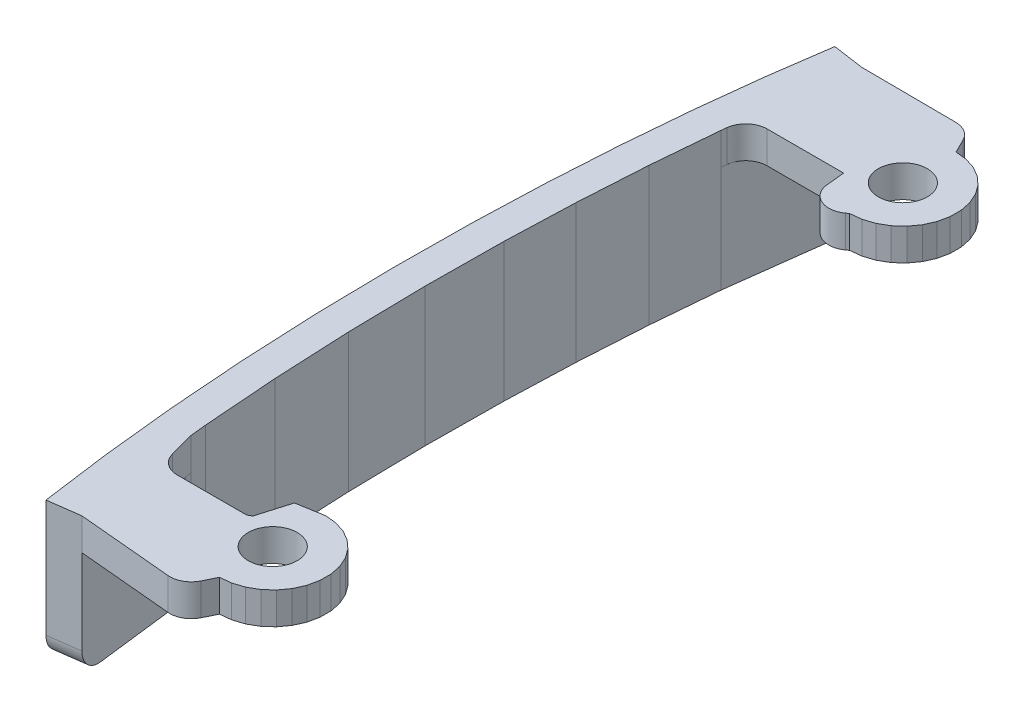
SolidWorks part; units mm, degrees
ref_plane "Płaszczyzna przednia" through (0, 0, 0) normal (0, 0, 1) x (1, 0, 0)
ref_plane "Płaszczyzna górna" through (0, 0, 0) normal (0, 1, 0) x (1, 0, 0)
ref_plane "Płaszczyzna prawa" through (0, 0, 0) normal (1, 0, 0) x (0, 0, -1)
sketch "Szkic2" plane through (0, 0.9904, 0) normal (0, 1, 0) x (1, 0, 0)
  line L0 (-173.5371, -25.6295) -> (-177.9802, -25.6005)
  line L3 (-173.6037, -62.5712) -> (-178.0582, -62.1645)
  line L4 (-179.4653, -25.3891) -> (-179.8753, -28.2702)
  line L5 (-179.8753, -28.2702) -> (-180.2209, -31.3158)
  line L6 (-180.2209, -31.3158) -> (-180.4963, -34.48)
  line L7 (-180.4963, -34.48) -> (-180.6936, -37.7356)
  line L8 (-180.6936, -37.7356) -> (-180.811, -41.0532)
  line L9 (-180.811, -41.0532) -> (-180.8444, -44.7704)
  line L10 (-180.8444, -44.7704) -> (-180.7766, -48.48)
  line L11 (-180.7766, -48.48) -> (-180.6066, -52.1372)
  line L12 (-180.6066, -52.1372) -> (-180.3404, -55.6994)
  line L13 (-180.3404, -55.6994) -> (-179.9818, -59.1279)
  line L14 (-179.9818, -59.1279) -> (-179.5448, -62.3651)
  line L15 (-177.9802, -25.6005) -> (-179.4653, -25.3891)
  line L16 (-178.0582, -62.1645) -> (-179.5448, -62.3651)
  line L17 (-178.8462, -55.5655) -> (-178.4922, -58.9495) construction
  line L18 (-178.7282, -31.4655) -> (-178.7001, -31.2172)
  line L19 (-178.3872, -28.4605) -> (-178.7282, -31.4655) construction
  line L20 (-177.7064, -30.33) -> (-174.1125, -30.33)
  line L22 (-172.3262, -56.4335) -> (-173.5902, -56.6495)
  line L23 (-173.5902, -56.6495) -> (-174.0356, -58.1605)
  line L24 (-174.0356, -58.1605) -> (-174.224, -58.263)
  line L25 (-174.224, -58.263) -> (-177.4828, -58.263)
  line L26 (-178.4487, -57.5219) -> (-178.7651, -56.3415)
  line L27 (-173.8462, -32.9335) -> (-172.3262, -31.8335) construction
  line L28 (-172.4416, -31.9169) -> (-172.3262, -31.8335)
  line L29 (-174.0227, -31.2086) -> (-174.1125, -30.33)
  line L155 (-167.3462, -84.1335) -> (-165.3462, -84.1335)
  line L156 (-165.3462, -84.1335) -> (-164.9012, -84.0835)
  line L157 (-164.9012, -84.0835) -> (-164.4782, -83.9355)
  line L158 (-164.4782, -83.9355) -> (-164.0992, -83.6975)
  line L159 (-164.0992, -83.6975) -> (-163.7822, -83.3805)
  line L160 (-163.7822, -83.3805) -> (-163.5442, -83.0015)
  line L161 (-163.5442, -83.0015) -> (-163.3962, -82.5785)
  line L162 (-163.3962, -82.5785) -> (-163.3462, -82.1335)
  line L163 (-163.3462, -82.1335) -> (-163.3462, -79.1335)
  line L164 (-163.3462, -79.1335) -> (-163.3962, -78.6885)
  line L165 (-163.3962, -78.6885) -> (-163.5442, -78.2655)
  line L166 (-163.5442, -78.2655) -> (-163.7822, -77.8865)
  line L167 (-163.7822, -77.8865) -> (-164.0992, -77.5695)
  line L168 (-164.0992, -77.5695) -> (-164.4782, -77.3315)
  line L169 (-164.4782, -77.3315) -> (-164.9012, -77.1835)
  line L170 (-164.9012, -77.1835) -> (-165.3462, -77.1335)
  line L171 (-165.3462, -77.1335) -> (-167.3462, -77.1335)
  line L172 (-167.3462, -77.1335) -> (-168.1752, -76.2025)
  line L173 (-168.1752, -76.2025) -> (-168.9292, -75.2375)
  line L174 (-168.9292, -75.2375) -> (-169.6902, -74.1145)
  line L175 (-169.6902, -74.1145) -> (-170.3542, -72.9535)
  line L176 (-170.3542, -72.9535) -> (-170.9242, -71.7535)
  line L177 (-170.9242, -71.7535) -> (-171.3582, -70.6365)
  line L178 (-171.3582, -70.6365) -> (-171.7182, -69.4815)
  line L179 (-171.7182, -69.4815) -> (-172.0032, -68.2855)
  line L180 (-172.0032, -68.2855) -> (-172.2152, -67.0325)
  line L181 (-172.2152, -67.0325) -> (-172.3462, -65.7435)
  line L182 (-172.3462, -65.7435) -> (-172.9212, -62.6335)
  line L183 (-172.9212, -62.6335) -> (-172.3262, -61.4335)
  line L184 (-172.3262, -61.4335) -> (-171.8062, -61.3785)
  line L185 (-171.8062, -61.3785) -> (-171.3092, -61.2175)
  line L186 (-171.3092, -61.2175) -> (-170.8562, -60.9565)
  line L187 (-170.8562, -60.9565) -> (-170.4682, -60.6065)
  line L188 (-170.4682, -60.6065) -> (-170.1612, -60.1835)
  line L189 (-170.1612, -60.1835) -> (-169.9482, -59.7065)
  line L190 (-169.9482, -59.7065) -> (-169.8402, -59.1945)
  line L191 (-169.8402, -59.1945) -> (-169.8402, -58.6725)
  line L192 (-169.8402, -58.6725) -> (-169.9482, -58.1605)
  line L193 (-169.9482, -58.1605) -> (-170.1612, -57.6835)
  line L194 (-170.1612, -57.6835) -> (-170.4682, -57.2605)
  line L195 (-170.4682, -57.2605) -> (-170.8562, -56.9105)
  line L196 (-170.8562, -56.9105) -> (-171.3092, -56.6495)
  line L197 (-171.3092, -56.6495) -> (-171.8062, -56.4885)
  line L198 (-171.8062, -56.4885) -> (-172.3262, -56.4335)
  line L199 (-172.3262, -56.4335) -> (-173.8462, -55.3335)
  line L200 (-173.8462, -55.3335) -> (-174.0262, -53.1335)
  line L201 (-174.0262, -53.1335) -> (-171.3462, -53.1335)
  line L202 (-171.3462, -53.1335) -> (-170.9012, -53.0835)
  line L203 (-170.9012, -53.0835) -> (-170.4782, -52.9355)
  line L204 (-170.4782, -52.9355) -> (-170.0992, -52.6975)
  line L205 (-170.0992, -52.6975) -> (-169.7822, -52.3805)
  line L206 (-169.7822, -52.3805) -> (-169.5442, -52.0015)
  line L207 (-169.5442, -52.0015) -> (-169.3962, -51.5785)
  line L208 (-169.3962, -51.5785) -> (-169.3462, -51.1335)
  line L209 (-169.3462, -51.1335) -> (-169.3462, -37.1335)
  line L210 (-169.3462, -37.1335) -> (-169.3962, -36.6885)
  line L211 (-169.3962, -36.6885) -> (-169.5442, -36.2655)
  line L212 (-169.5442, -36.2655) -> (-169.7822, -35.8865)
  line L213 (-169.7822, -35.8865) -> (-170.0992, -35.5695)
  line L214 (-170.0992, -35.5695) -> (-170.4782, -35.3315)
  line L215 (-170.4782, -35.3315) -> (-170.9012, -35.1835)
  line L216 (-170.9012, -35.1835) -> (-171.3462, -35.1335)
  line L217 (-171.3462, -35.1335) -> (-174.0262, -35.1335)
  line L218 (-174.0262, -35.1335) -> (-173.8462, -32.9335)
  line L219 (-173.8462, -32.9335) -> (-172.3262, -31.8335)
  line L220 (-172.3262, -31.8335) -> (-171.8062, -31.7785)
  line L221 (-171.8062, -31.7785) -> (-171.3092, -31.6175)
  line L222 (-171.3092, -31.6175) -> (-170.8562, -31.3565)
  line L223 (-170.8562, -31.3565) -> (-170.4682, -31.0065)
  line L224 (-170.4682, -31.0065) -> (-170.1612, -30.5835)
  line L225 (-170.1612, -30.5835) -> (-169.9482, -30.1065)
  line L226 (-169.9482, -30.1065) -> (-169.8402, -29.5945)
  line L227 (-169.8402, -29.5945) -> (-169.8402, -29.0725)
  line L228 (-169.8402, -29.0725) -> (-169.9482, -28.5605)
  line L229 (-169.9482, -28.5605) -> (-170.1612, -28.0835)
  line L230 (-170.1612, -28.0835) -> (-170.4682, -27.6605)
  line L231 (-170.4682, -27.6605) -> (-170.8562, -27.3105)
  line L232 (-170.8562, -27.3105) -> (-171.3092, -27.0495)
  line L233 (-171.3092, -27.0495) -> (-171.8062, -26.8885)
  line L234 (-171.8062, -26.8885) -> (-172.3262, -26.8335)
  line L235 (-172.3262, -26.8335) -> (-172.9212, -25.6335)
  line L236 (-172.9212, -25.6335) -> (-172.3462, -22.5235)
  line L237 (-172.3462, -22.5235) -> (-172.2152, -21.2345)
  line L238 (-172.2152, -21.2345) -> (-172.0032, -19.9815)
  line L239 (-172.0032, -19.9815) -> (-171.7182, -18.7855)
  line L240 (-171.7182, -18.7855) -> (-171.3582, -17.6305)
  line L241 (-171.3582, -17.6305) -> (-170.9242, -16.5135)
  line L242 (-170.9242, -16.5135) -> (-170.3542, -15.3135)
  line L243 (-170.3542, -15.3135) -> (-169.6902, -14.1525)
  line L244 (-169.6902, -14.1525) -> (-168.9292, -13.0295)
  line L245 (-168.9292, -13.0295) -> (-168.1752, -12.0645)
  line L246 (-168.1752, -12.0645) -> (-167.3462, -11.1335)
  line L247 (-167.3462, -11.1335) -> (-165.3462, -11.1335)
  line L248 (-165.3462, -11.1335) -> (-164.9012, -11.0835)
  line L249 (-164.9012, -11.0835) -> (-164.4782, -10.9355)
  line L250 (-164.4782, -10.9355) -> (-164.0992, -10.6975)
  line L251 (-164.0992, -10.6975) -> (-163.7822, -10.3805)
  line L252 (-163.7822, -10.3805) -> (-163.5442, -10.0015)
  line L253 (-163.5442, -10.0015) -> (-163.3962, -9.5785)
  line L254 (-163.3962, -9.5785) -> (-163.3462, -9.1335)
  line L255 (-163.3462, -9.1335) -> (-163.3462, -6.1335)
  line L256 (-163.3462, -6.1335) -> (-163.3962, -5.6885)
  line L257 (-163.3962, -5.6885) -> (-163.5442, -5.2655)
  line L258 (-163.5442, -5.2655) -> (-163.7822, -4.8865)
  line L259 (-163.7822, -4.8865) -> (-164.0992, -4.5695)
  line L260 (-164.0992, -4.5695) -> (-164.4782, -4.3315)
  line L261 (-164.4782, -4.3315) -> (-164.9012, -4.1835)
  line L262 (-164.9012, -4.1835) -> (-165.3462, -4.1335)
  line L263 (-165.3462, -4.1335) -> (-167.3462, -4.1335)
  line L264 (-167.3462, -4.1335) -> (-167.9032, -4.1765)
  line L265 (-167.9032, -4.1765) -> (-168.4842, -4.3135)
  line L266 (-168.4842, -4.3135) -> (-169.0482, -4.5375)
  line L267 (-169.0482, -4.5375) -> (-169.6222, -4.8595)
  line L268 (-169.6222, -4.8595) -> (-170.2082, -5.2875)
  line L269 (-170.2082, -5.2875) -> (-170.8082, -5.8345)
  line L270 (-170.8082, -5.8345) -> (-171.4912, -6.5955)
  line L271 (-171.4912, -6.5955) -> (-172.1892, -7.5355)
  line L272 (-172.1892, -7.5355) -> (-172.8982, -8.6725)
  line L273 (-172.8982, -8.6725) -> (-173.6142, -10.0245)
  line L274 (-173.6142, -10.0245) -> (-174.3302, -11.6055)
  line L275 (-174.3302, -11.6055) -> (-175.0362, -13.4275)
  line L276 (-175.0362, -13.4275) -> (-175.7252, -15.4985)
  line L277 (-175.7252, -15.4985) -> (-176.3842, -17.8195)
  line L278 (-176.3842, -17.8195) -> (-177.0032, -20.3885)
  line L279 (-177.0032, -20.3885) -> (-177.5162, -22.9035)
  line L280 (-177.5162, -22.9035) -> (-177.9802, -25.6005)
  line L281 (-177.9802, -25.6005) -> (-178.3872, -28.4605)
  line L282 (-178.3872, -28.4605) -> (-178.7282, -31.4655)
  line L283 (-178.7282, -31.4655) -> (-179.0002, -34.5905)
  line L284 (-179.0002, -34.5905) -> (-179.1952, -37.8075)
  line L285 (-179.1952, -37.8075) -> (-179.3112, -41.0865)
  line L286 (-179.3112, -41.0865) -> (-179.3442, -44.7635)
  line L287 (-179.3442, -44.7635) -> (-179.2772, -48.4315)
  line L288 (-179.2772, -48.4315) -> (-179.1092, -52.0465)
  line L289 (-179.1092, -52.0465) -> (-178.8462, -55.5655)
  line L290 (-178.8462, -55.5655) -> (-178.4922, -58.9495)
  line L291 (-178.4922, -58.9495) -> (-178.0582, -62.1645)
  line L292 (-178.0582, -62.1645) -> (-177.5502, -65.1805)
  line L293 (-177.5502, -65.1805) -> (-176.9812, -67.9765)
  line L294 (-176.9812, -67.9765) -> (-176.3612, -70.5355)
  line L295 (-176.3612, -70.5355) -> (-175.7002, -72.8475)
  line L296 (-175.7002, -72.8475) -> (-175.0112, -74.9105)
  line L297 (-175.0112, -74.9105) -> (-174.3742, -76.5555)
  line L298 (-174.3742, -76.5555) -> (-173.7292, -78.0045)
  line L299 (-173.7292, -78.0045) -> (-173.0822, -79.2675)
  line L300 (-173.0822, -79.2675) -> (-172.4392, -80.3515)
  line L301 (-172.4392, -80.3515) -> (-171.8042, -81.2705)
  line L302 (-171.8042, -81.2705) -> (-171.1812, -82.0355)
  line L303 (-171.1812, -82.0355) -> (-170.5722, -82.6605)
  line L304 (-170.5722, -82.6605) -> (-169.9142, -83.2075)
  line L305 (-169.9142, -83.2075) -> (-169.2752, -83.6135)
  line L306 (-169.2752, -83.6135) -> (-168.6542, -83.8955)
  line L307 (-168.6542, -83.8955) -> (-168.0482, -84.0645)
  line L308 (-168.0482, -84.0645) -> (-167.6922, -84.1165)
  line L309 (-167.6922, -84.1165) -> (-167.3462, -84.1335)
  line L338 (-172.6168, -62.0195) -> (-172.3262, -61.4335)
  line L339 (-172.3262, -61.4335) -> (-171.8062, -61.3785)
  line L340 (-171.8062, -61.3785) -> (-171.3092, -61.2175)
  line L341 (-171.3092, -61.2175) -> (-170.8562, -60.9565)
  line L342 (-170.8562, -60.9565) -> (-170.4682, -60.6065)
  line L343 (-170.4682, -60.6065) -> (-170.1612, -60.1835)
  line L344 (-170.1612, -60.1835) -> (-169.9482, -59.7065)
  line L345 (-169.9482, -59.7065) -> (-169.8402, -59.1945)
  line L346 (-169.8402, -59.1945) -> (-169.8402, -58.6725)
  line L347 (-169.8402, -58.6725) -> (-169.9482, -58.1605)
  line L348 (-169.9482, -58.1605) -> (-170.1612, -57.6835)
  line L349 (-170.1612, -57.6835) -> (-170.4682, -57.2605)
  line L350 (-170.4682, -57.2605) -> (-170.8562, -56.9105)
  line L351 (-170.8562, -56.9105) -> (-171.3092, -56.6495)
  line L352 (-171.3092, -56.6495) -> (-171.8062, -56.4885)
  line L353 (-171.8062, -56.4885) -> (-172.3262, -56.4335)
  line L375 (-172.3262, -31.8335) -> (-171.8062, -31.7785)
  line L376 (-171.8062, -31.7785) -> (-171.3092, -31.6175)
  line L377 (-171.3092, -31.6175) -> (-170.8562, -31.3565)
  line L378 (-170.8562, -31.3565) -> (-170.4682, -31.0065)
  line L379 (-170.4682, -31.0065) -> (-170.1612, -30.5835)
  line L380 (-170.1612, -30.5835) -> (-169.9482, -30.1065)
  line L381 (-169.9482, -30.1065) -> (-169.8402, -29.5945)
  line L382 (-169.8402, -29.5945) -> (-169.8402, -29.0725)
  line L383 (-169.8402, -29.0725) -> (-169.9482, -28.5605)
  line L384 (-169.9482, -28.5605) -> (-170.1612, -28.0835)
  line L385 (-170.1612, -28.0835) -> (-170.4682, -27.6605)
  line L386 (-170.4682, -27.6605) -> (-170.8562, -27.3105)
  line L387 (-170.8562, -27.3105) -> (-171.3092, -27.0495)
  line L388 (-171.3092, -27.0495) -> (-171.8062, -26.8885)
  line L389 (-171.8062, -26.8885) -> (-172.3262, -26.8335)
  line L390 (-172.3262, -26.8335) -> (-172.6477, -26.1852)
  line L438 (-178.7282, -31.4655) -> (-179.0002, -34.5905)
  line L439 (-179.0002, -34.5905) -> (-179.1952, -37.8075)
  line L440 (-179.1952, -37.8075) -> (-179.3112, -41.0865)
  line L441 (-179.3112, -41.0865) -> (-179.3442, -44.7635)
  line L442 (-179.3442, -44.7635) -> (-179.2772, -48.4315)
  line L443 (-179.2772, -48.4315) -> (-179.1092, -52.0465)
  line L444 (-179.1092, -52.0465) -> (-178.8462, -55.5655)
  line L445 (-178.8462, -55.5655) -> (-178.7651, -56.3415)
  line L459 (-178.3872, -28.4605) -> (-178.7282, -31.4655) construction
  line L460 (-177.9802, -25.6005) -> (-178.3872, -28.4605) construction
  line L461 (-178.4922, -58.9495) -> (-178.0582, -62.1645) construction
  arc A0 (-173.5371, -25.6295) -> (-172.6477, -26.1852) centre (-173.5436, -26.6294) cw
  circle A1 centre (-172.326, -29.3335) radius 1.15
  circle A2 centre (-172.326, -29.3335) radius 1.15
  circle A3 centre (-172.326, -58.9335) radius 1.15
  circle A4 centre (-172.326, -58.9335) radius 1.15
  arc A5 (-178.7001, -31.2172) -> (-177.7064, -30.33) centre (-177.7064, -31.33) cw
  arc A6 (-178.4487, -57.5219) -> (-177.4828, -58.263) centre (-177.4828, -57.263) ccw
  arc A7 (-172.6168, -62.0195) -> (-173.6037, -62.5712) centre (-173.5127, -61.5753) cw
  arc A8 (-172.4416, -31.9169) -> (-174.0227, -31.2086) centre (-173.0278, -31.1068) cw
  point P60 (-178.5994, -30.33)
  dimension "D5" = 1
  dimension "D6" = 1
  dimension "D1" = 0
  dimension "D2" = 0
  dimension "D3" = 0
  dimension "D4" = 1.5
extrude "Dodanie-wyciągnięcie1" add sketch "Szkic2" along normal blind 1.5
sketch "Szkic3" plane through (0, 0.9904, 0) normal (0, -1, 0) x (1, 0, 0)
  line L0 (-178.7651, 56.3415) -> (-178.0582, 62.1645)
  line L1 (-178.0582, 62.1645) -> (-179.5448, 62.3651)
  line L2 (-179.4653, 25.3891) -> (-177.9802, 25.6005)
  line L3 (-177.9802, 25.6005) -> (-178.7282, 31.4655)
  line L64 (-179.4653, 25.3891) -> (-177.9802, 25.6005)
  line L65 (-177.9802, 25.6005) -> (-173.5371, 25.6295)
  line L66 (-172.6477, 26.1852) -> (-172.3262, 26.8335)
  line L67 (-172.3262, 26.8335) -> (-171.8062, 26.8885)
  line L68 (-171.8062, 26.8885) -> (-171.3092, 27.0495)
  line L69 (-171.3092, 27.0495) -> (-170.8562, 27.3105)
  line L70 (-170.8562, 27.3105) -> (-170.4682, 27.6605)
  line L71 (-170.4682, 27.6605) -> (-170.1612, 28.0835)
  line L72 (-170.1612, 28.0835) -> (-169.9482, 28.5605)
  line L73 (-169.9482, 28.5605) -> (-169.8402, 29.0725)
  line L74 (-169.8402, 29.0725) -> (-169.8402, 29.5945)
  line L75 (-169.8402, 29.5945) -> (-169.9482, 30.1065)
  line L76 (-169.9482, 30.1065) -> (-170.1612, 30.5835)
  line L77 (-170.1612, 30.5835) -> (-170.4682, 31.0065)
  line L78 (-170.4682, 31.0065) -> (-170.8562, 31.3565)
  line L79 (-170.8562, 31.3565) -> (-171.3092, 31.6175)
  line L80 (-171.3092, 31.6175) -> (-171.8062, 31.7785)
  line L81 (-171.8062, 31.7785) -> (-172.3262, 31.8335)
  line L82 (-172.3262, 31.8335) -> (-172.4416, 31.9169)
  line L83 (-174.0227, 31.2086) -> (-174.1125, 30.33)
  line L84 (-174.1125, 30.33) -> (-177.7064, 30.33)
  line L85 (-178.7001, 31.2172) -> (-178.7282, 31.4655)
  line L86 (-178.7282, 31.4655) -> (-179.0002, 34.5905)
  line L87 (-179.0002, 34.5905) -> (-179.1952, 37.8075)
  line L88 (-179.1952, 37.8075) -> (-179.3112, 41.0865)
  line L89 (-179.3112, 41.0865) -> (-179.3442, 44.7635)
  line L90 (-179.3442, 44.7635) -> (-179.2772, 48.4315)
  line L91 (-179.2772, 48.4315) -> (-179.1092, 52.0465)
  line L92 (-179.1092, 52.0465) -> (-178.8462, 55.5655)
  line L93 (-178.8462, 55.5655) -> (-178.7651, 56.3415)
  line L94 (-178.7651, 56.3415) -> (-178.4487, 57.5219)
  line L95 (-177.4828, 58.263) -> (-174.224, 58.263)
  line L96 (-174.224, 58.263) -> (-174.0356, 58.1605)
  line L97 (-174.0356, 58.1605) -> (-173.5902, 56.6495)
  line L98 (-173.5902, 56.6495) -> (-172.3262, 56.4335)
  line L99 (-172.3262, 56.4335) -> (-171.8062, 56.4885)
  line L100 (-171.8062, 56.4885) -> (-171.3092, 56.6495)
  line L101 (-171.3092, 56.6495) -> (-170.8562, 56.9105)
  line L102 (-170.8562, 56.9105) -> (-170.4682, 57.2605)
  line L103 (-170.4682, 57.2605) -> (-170.1612, 57.6835)
  line L104 (-170.1612, 57.6835) -> (-169.9482, 58.1605)
  line L105 (-169.9482, 58.1605) -> (-169.8402, 58.6725)
  line L106 (-169.8402, 58.6725) -> (-169.8402, 59.1945)
  line L107 (-169.8402, 59.1945) -> (-169.9482, 59.7065)
  line L108 (-169.9482, 59.7065) -> (-170.1612, 60.1835)
  line L109 (-170.1612, 60.1835) -> (-170.4682, 60.6065)
  line L110 (-170.4682, 60.6065) -> (-170.8562, 60.9565)
  line L111 (-170.8562, 60.9565) -> (-171.3092, 61.2175)
  line L112 (-171.3092, 61.2175) -> (-171.8062, 61.3785)
  line L113 (-171.8062, 61.3785) -> (-172.3262, 61.4335)
  line L114 (-172.3262, 61.4335) -> (-172.6168, 62.0195)
  line L115 (-173.6037, 62.5712) -> (-178.0582, 62.1645)
  line L116 (-178.0582, 62.1645) -> (-179.5448, 62.3651)
  line L117 (-179.5448, 62.3651) -> (-179.9818, 59.1279)
  line L118 (-179.9818, 59.1279) -> (-180.3404, 55.6994)
  line L119 (-180.3404, 55.6994) -> (-180.6066, 52.1372)
  line L120 (-180.6066, 52.1372) -> (-180.7766, 48.48)
  line L121 (-180.7766, 48.48) -> (-180.8444, 44.7704)
  line L122 (-180.8444, 44.7704) -> (-180.811, 41.0532)
  line L123 (-180.811, 41.0532) -> (-180.6936, 37.7356)
  line L124 (-180.6936, 37.7356) -> (-180.4963, 34.48)
  line L125 (-180.4963, 34.48) -> (-180.2209, 31.3158)
  line L126 (-180.2209, 31.3158) -> (-179.8753, 28.2702)
  line L127 (-179.8753, 28.2702) -> (-179.4653, 25.3891)
  line L150 (-178.7282, 31.4655) -> (-179.0002, 34.5905)
  line L151 (-179.0002, 34.5905) -> (-179.1952, 37.8075)
  line L152 (-179.1952, 37.8075) -> (-179.3112, 41.0865)
  line L153 (-179.3112, 41.0865) -> (-179.3442, 44.7635)
  line L154 (-179.3442, 44.7635) -> (-179.2772, 48.4315)
  line L155 (-179.2772, 48.4315) -> (-179.1092, 52.0465)
  line L156 (-179.1092, 52.0465) -> (-178.8462, 55.5655)
  line L157 (-178.8462, 55.5655) -> (-178.7651, 56.3415)
  line L181 (-179.5448, 62.3651) -> (-179.9818, 59.1279)
  line L182 (-179.9818, 59.1279) -> (-180.3404, 55.6994)
  line L183 (-180.3404, 55.6994) -> (-180.6066, 52.1372)
  line L184 (-180.6066, 52.1372) -> (-180.7766, 48.48)
  line L185 (-180.7766, 48.48) -> (-180.8444, 44.7704)
  line L186 (-180.8444, 44.7704) -> (-180.811, 41.0532)
  line L187 (-180.811, 41.0532) -> (-180.6936, 37.7356)
  line L188 (-180.6936, 37.7356) -> (-180.4963, 34.48)
  line L189 (-180.4963, 34.48) -> (-180.2209, 31.3158)
  line L190 (-180.2209, 31.3158) -> (-179.8753, 28.2702)
  line L191 (-179.8753, 28.2702) -> (-179.4653, 25.3891)
  arc A5 (-173.5371, 25.6295) -> (-172.6477, 26.1852) centre (-173.5436, 26.6294) ccw
  arc A6 (-172.4416, 31.9169) -> (-174.0227, 31.2086) centre (-173.0278, 31.1068) ccw
  arc A7 (-178.7001, 31.2172) -> (-177.7064, 30.33) centre (-177.7064, 31.33) ccw
  arc A8 (-177.4828, 58.263) -> (-178.4487, 57.5219) centre (-177.4828, 57.263) ccw
  arc A9 (-172.6168, 62.0195) -> (-173.6037, 62.5712) centre (-173.5127, 61.5753) ccw
  dimension "D1" = 0
extrude "Dodanie-wyciągnięcie2" add sketch "Szkic3" along normal blind 5
fillet "Zaokrąglenie1" radius 1 2 edges at (-178.8015, -4.0096, 62.2648) (-178.7228, -4.0096, 25.4948)
